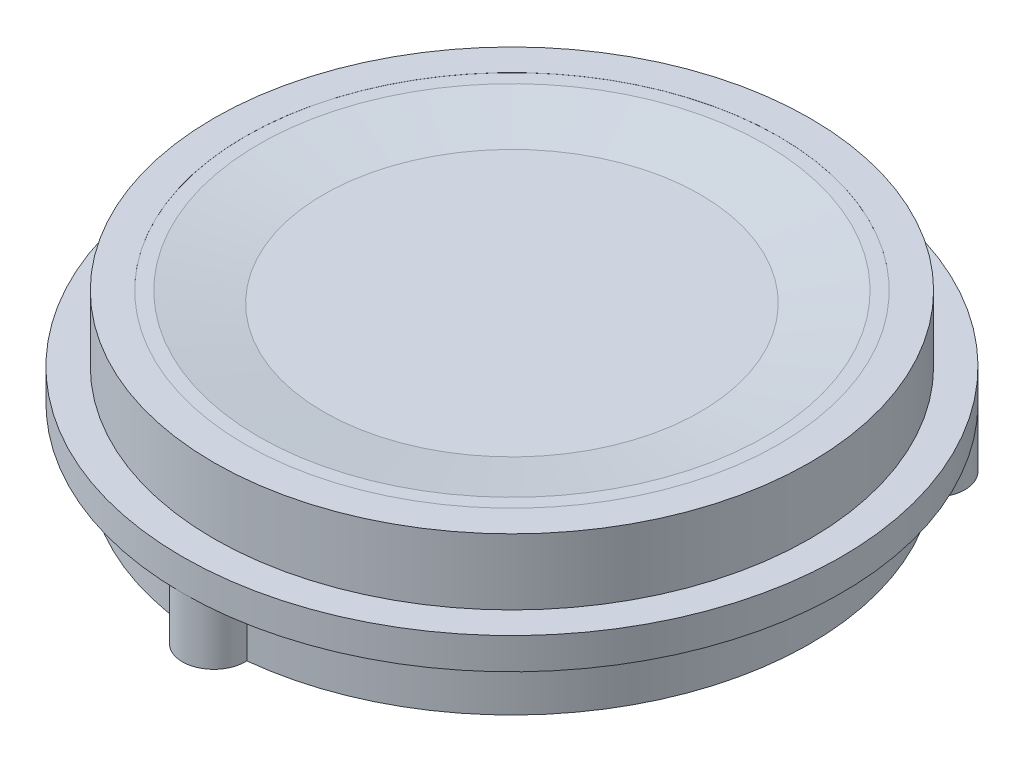
SolidWorks part; units mm, degrees
ref_plane "前视基准面" through (0, 0, 0) normal (0, 0, 1) x (1, 0, 0)
ref_plane "上视基准面" through (0, 0, 0) normal (0, 1, 0) x (1, 0, 0)
ref_plane "右视基准面" through (0, 0, 0) normal (1, 0, 0) x (0, 0, -1)
other "Configuration Table"
sketch "草图1" plane through (0, 0, 0) normal (0, 1, 0) x (1, 0, 0)
  circle A0 centre (0, 0) radius 9.5
  dimension "D1" = 19
extrude "凸台-拉伸1" add sketch "草图1" along normal blind 5
sketch "草图2" plane through (0, 5, 0) normal (0, 1, 0) x (1, 0, 0)
  circle A0 centre (0, 0) radius 10.5
  dimension "D1" = 21
extrude "凸台-拉伸2" add sketch "草图2" against normal blind 1 from offset 2.1 offset against normal yes
sketch "草图4" plane through (0, 0, 0) normal (0, 0, 1) x (1, 0, 0)
  line L0 (0, -1.5174) -> (0, 7.1371) construction
  line L1 (9.5, 5) -> (-9.5, 5) construction
  line L2 (-6, 4.6479) -> (-8.0699, 4.9973)
  line L4 (-6, 4.6479) -> (0, 4.6479)
  line L5 (0, 4.6479) -> (0, 5)
  line L6 (0, 5) -> (-8.5, 5)
  line L8 (-8.0699, 4.9973) -> (-8.5, 4.9973)
  line L9 (-8.5, 4.9973) -> (-8.5, 5)
  dimension "D1" = 6
  dimension "D2" = 2.5
revolve "切除-旋转1" cut sketch "草图4" angle 360 about L0
sketch "草图5" plane through (0, 0, 0) normal (0, -1, 0) x (1, 0, 0)
  circle A0 centre (0, 9.5) radius 1
  circle A1 centre (0, 0) radius 10.5 construction
  point P4 (0, 0)
  point P7 (0, 0)
  dimension "D1" = 2
extrude "凸台-拉伸3" add sketch "草图5" against normal up to surface (1.9 mm away) up to face at (0, 1.9, 9.5)
sketch "草图6" plane through (0, 0, 0) normal (0, 0, 1) x (1, 0, 0)
  line L0 (0, -1.4747) -> (0, 8.3979) construction
pattern_circular "阵列(圆周)1" count 2 over 135 about axis through (0, -1.4747, 0) along (0, 1, 0) of "凸台-拉伸3"
pattern_circular "阵列(圆周)2" count 2 over 135 about axis through (0, -1.4747, 0) along (0, 1, 0) of "阵列(圆周)1" reverse direction yes
sketch "草图7" plane through (0, 0, 0) normal (0, -1, 0) x (1, 0, 0)
  line L0 (0, 11.3659) -> (0, -12.2785) construction
  line L2 (4.9, -5.108) -> (-4.9, -5.108)
  line L3 (5.9, -4.108) -> (5.9, -1.308)
  line L4 (4.9, -0.308) -> (-4.9, -0.308)
  line L5 (-5.9, -4.108) -> (-5.9, -1.308)
  line L6 (5.9, -5.108) -> (-5.9, -0.308) construction
  line L7 (5.9, -0.308) -> (-5.9, -5.108) construction
  arc A0 (5.9, -1.308) -> (4.9, -0.308) centre (4.9, -1.308) ccw
  arc A1 (4.9, -5.108) -> (5.9, -4.108) centre (4.9, -4.108) ccw
  arc A2 (-4.9, -5.108) -> (-5.9, -4.108) centre (-4.9, -4.108) cw
  arc A3 (-5.9, -1.308) -> (-4.9, -0.308) centre (-4.9, -1.308) cw
  point P3 (0, -2.708)
  point P8 (0, 0)
  point P9 (0, -2.708)
  point P10 (0, 0)
  dimension "D3" = 1
  dimension "D1" = 4.8
  dimension "D2" = 11.8
extrude "切除-拉伸1" cut sketch "草图7" against normal blind 3
sketch "草图8" plane through (0, 3, 0) normal (0, -1, 0) x (1, 0, 0)
  line L0 (0, 11.2277) -> (0, -11.5872) construction
  line L1 (-12.1402, -2.708) -> (11.1723, -2.708) construction
  line L3 (4, -1.208) -> (-4, -1.208)
  line L4 (4, -1.208) -> (4, -4.208)
  line L5 (4, -4.208) -> (-4, -4.208)
  line L6 (-4, -1.208) -> (-4, -4.208)
  line L7 (4, -1.208) -> (-4, -4.208) construction
  line L8 (4, -4.208) -> (-4, -1.208) construction
  point P5 (0, -2.708)
  dimension "D1" = 8
  dimension "D2" = 3
extrude "凸台-拉伸4" add sketch "草图8" along normal blind 4
sketch "草图9" plane through (0, -1, 0) normal (0, -1, 0) x (1, 0, 0)
  line L0 (0, 14.6169) -> (0, -13.163) construction
  line L1 (3.065, -1.6504) -> (-3.065, -1.6504)
  line L2 (-3.065, -1.6504) -> (-3.065, -2.2038)
  line L3 (-3.065, -2.2038) -> (-3.629, -2.2038)
  line L4 (-3.629, -2.2038) -> (-3.629, -2.7696)
  line L5 (-3.629, -2.7696) -> (-3.2765, -2.7696)
  line L6 (-3.2765, -2.7696) -> (-3.2765, -3.6996)
  line L7 (-3.2765, -3.6996) -> (3.2765, -3.6996)
  line L8 (3.2765, -2.7696) -> (3.2765, -3.6996)
  line L9 (3.629, -2.7696) -> (3.2765, -2.7696)
  line L10 (3.629, -2.2038) -> (3.629, -2.7696)
  line L11 (3.065, -2.2038) -> (3.629, -2.2038)
  line L12 (3.065, -1.6504) -> (3.065, -2.2038)
  line L13 (-4, -1.208) -> (-4, -4.208) construction
  line L14 (-4, -3.8362) -> (-3.629, -3.8362)
  line L15 (-4, -3.8362) -> (-4, -4.208)
  line L16 (-4, -4.208) -> (-3.629, -4.208)
  line L17 (-3.629, -3.8362) -> (-3.629, -4.208)
  line L18 (-4, -4.208) -> (4, -4.208) construction
  line L19 (4, -4.208) -> (4, -1.208) construction
  line L20 (4, -3.8362) -> (3.629, -3.8362)
  line L21 (4, -3.8362) -> (4, -4.208)
  line L22 (4, -4.208) -> (3.629, -4.208)
  line L23 (3.629, -3.8362) -> (3.629, -4.208)
  point P12 (0, -3.6996)
  point P17 (0, -1.6504)
extrude "切除-拉伸2" cut sketch "草图9" against normal blind 3
sketch "草图10" plane through (0, 2, 0) normal (0, -1, 0) x (1, 0, 0)
  line L1 (-2.6349, -2.2271) -> (-2.3349, -2.2271)
  line L2 (-2.6349, -2.2271) -> (-2.6349, -2.5271)
  line L3 (-2.6349, -2.5271) -> (-2.3349, -2.5271)
  line L4 (-2.3349, -2.2271) -> (-2.3349, -2.5271)
  dimension "D1" = 0.3
  dimension "D2" = 0.3
extrude "凸台-拉伸5" add sketch "草图10" along normal blind 2.5
pattern_linear "阵列(线性)1" count 6 spacing 1 along (1, 0, 0) of "凸台-拉伸5"
chamfer "倒角2" distance 0.1 angle 45 24 edges at (1.5151, -0.5, -2.2271) (1.6651, -0.5, -2.3771) (1.5151, -0.5, -2.5271) (1.3651, -0.5, -2.3771) (2.5151, -0.5, -2.2271) (2.6651, -0.5, -2.3771) (2.5151, -0.5, -2.5271) (2.3651, -0.5, -2.3771) (0.5151, -0.5, -2.2271) (0.6651, -0.5, -2.3771) (0.5151, -0.5, -2.5271) (0.3651, -0.5, -2.3771) (-0.4849, -0.5, -2.2271) (-0.3349, -0.5, -2.3771) (-0.4849, -0.5, -2.5271) (-0.6349, -0.5, -2.3771) (-1.4849, -0.5, -2.2271) (-1.3349, -0.5, -2.3771) (-1.4849, -0.5, -2.5271) (-1.6349, -0.5, -2.3771) (-2.4849, -0.5, -2.2271) (-2.3349, -0.5, -2.3771) (-2.4849, -0.5, -2.5271) (-2.6349, -0.5, -2.3771)
sketch "草图12" plane through (0, 0, 0) normal (0, -1, 0) x (1, 0, 0)
  line L0 (5.9, -4.108) -> (5.9, -1.308) construction
  line L1 (-4.9, -5.108) -> (4.9, -5.108) construction
  line L2 (-5.9, -1.308) -> (-5.9, -4.108) construction
  line L3 (4.9, -0.308) -> (-4.9, -0.308) construction
  line L4 (5.9, -4.108) -> (5.9, -1.308)
  line L5 (-4.9, -5.108) -> (4.9, -5.108)
  line L6 (-5.9, -1.308) -> (-5.9, -4.108)
  line L7 (4.9, -0.308) -> (-4.9, -0.308)
  arc A0 (5.9, -1.308) -> (4.9, -0.308) centre (4.9, -1.308) ccw construction
  arc A1 (4.9, -5.108) -> (5.9, -4.108) centre (4.9, -4.108) ccw construction
  arc A2 (-5.9, -4.108) -> (-4.9, -5.108) centre (-4.9, -4.108) ccw construction
  arc A3 (-4.9, -0.308) -> (-5.9, -1.308) centre (-4.9, -1.308) ccw construction
  arc A4 (5.9, -1.308) -> (4.9, -0.308) centre (4.9, -1.308) ccw
  arc A5 (4.9, -5.108) -> (5.9, -4.108) centre (4.9, -4.108) ccw
  arc A6 (-5.9, -4.108) -> (-4.9, -5.108) centre (-4.9, -4.108) ccw
  arc A7 (-4.9, -0.308) -> (-5.9, -1.308) centre (-4.9, -1.308) ccw
  circle A8 centre (0, 0) radius 9
  dimension "D1" = 18
extrude "切除-拉伸3" cut sketch "草图12" against normal up to surface (3 mm away) from offset 0.5 up to face at (0, 3, -2.708) offset against normal yes
